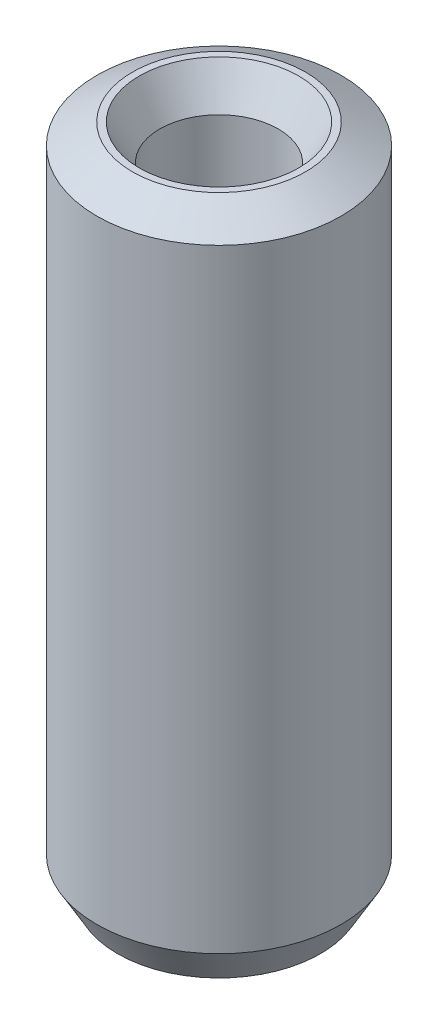
SolidWorks part; units mm, degrees
ref_plane "Front Plane" through (0, 0, 0) normal (0, 0, 1) x (1, 0, 0)
ref_plane "Top Plane" through (0, 0, 0) normal (0, 1, 0) x (1, 0, 0)
ref_plane "Right Plane" through (0, 0, 0) normal (1, 0, 0) x (0, 0, -1)
sketch "Sketch1" plane through (0, 0, 0) normal (0, 1, 0) x (1, 0, 0)
  circle A0 centre (0, 0) radius 17.5
  dimension "SLEEVE_OD" = 35
extrude "Boss-Extrude1" add sketch "Sketch1" along normal blind 95.9808
sketch "Sketch2" plane through (0, 0, 0) normal (0, 1, 0) x (1, 0, 0)
  circle A0 centre (0, 0) radius 8.483
  dimension "BORE_D" = 16.966
extrude "Cut-Extrude1" cut sketch "Sketch2" along normal through all
chamfer "Chamfer1" distance 2.9444 angle 60 4 edges at (0, 95.9808, 8.483) (0, 0, 8.483) (0, 0, 17.5) (0, 95.9808, 17.5) first distance on face at (0, 95.9808, 8.483) first distance on face at (0, 0, 8.483) first distance on face at (0, 95.9808, 17.5)
